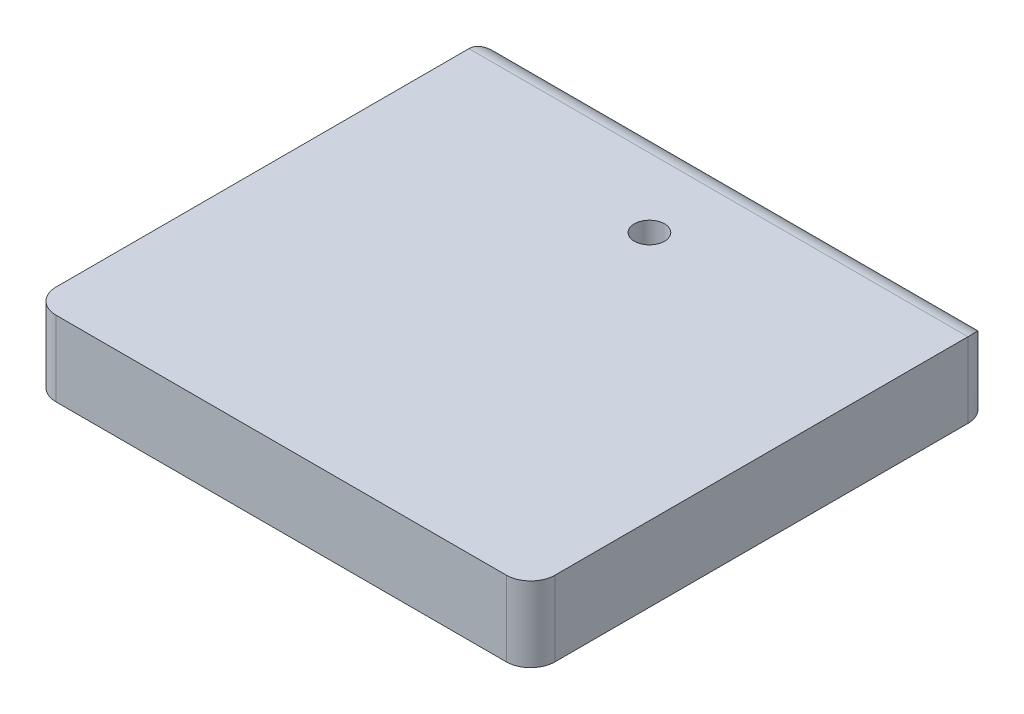
SolidWorks part; units mm, degrees
material "Wooden Hook Mount"
ref_plane "Front Plane" through (0, 0, 0) normal (0, 0, 1) x (1, 0, 0)
ref_plane "Top Plane" through (0, 0, 0) normal (0, 1, 0) x (1, 0, 0)
ref_plane "Right Plane" through (0, 0, 0) normal (1, 0, 0) x (0, 0, -1)
sketch "Sketch1" plane through (0, 0, 0) normal (0, 1, 0) x (1, 0, 0)
  line L1 (0, 0) -> (51.9684, 0)
  line L2 (0, 0) -> (0, 48.0822)
  line L3 (0, 48.0822) -> (51.9684, 48.0822)
  line L4 (51.9684, 0) -> (51.9684, 48.0822)
  dimension "D1" = 51.9684
  dimension "D2" = 48.0822
extrude "Boss-Extrude1" add sketch "Sketch1" along normal blind 7.8232
fillet "Fillet1" radius 2.54 4 edges at (51.9684, 3.9116, 0) (0, 3.9116, 0) (0, 3.9116, -48.0822) (51.9684, 3.9116, -48.0822)
fillet "Fillet2" radius 2.54 1 edges at (25.9842, 7.8232, -48.0822) tangent propagation no
ref_plane "Plane1" through (25.9842, 0, 0) normal (1, 0, 0) x (0, 0, -1)
sketch "Sketch3" plane through (0, 7.8232, 0) normal (0, 1, 0) x (1, 0, 0)
  line L0 (2.54, 48.0822) -> (49.4284, 48.0822) construction
  line L1 (25.9842, 45.5422) -> (25.9842, 22.0443) construction
  line L2 (51.9684, 45.5422) -> (0, 45.5422) construction
  circle A0 centre (25.9842, 38.354) radius 1.5748
  dimension "D1" = 3.1496
  dimension "D2" = 9.7282
  dimension "D3" = 9.7282
extrude "Cut-Extrude1" cut sketch "Sketch3" against normal through all
